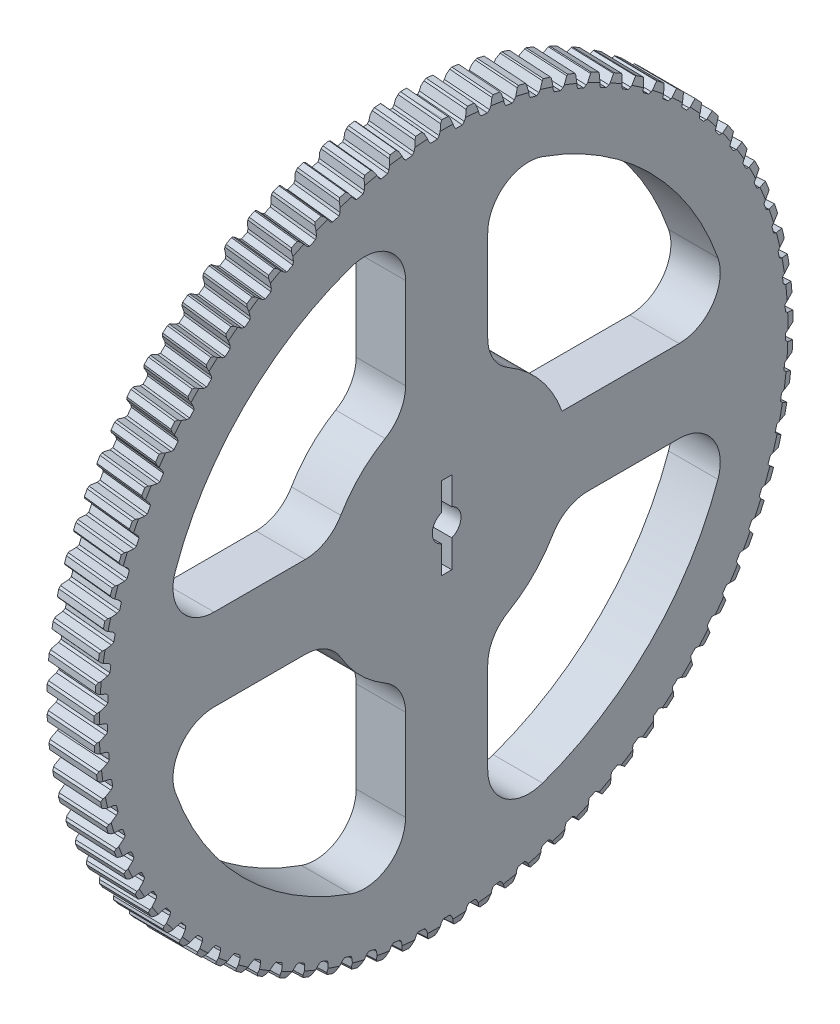
SolidWorks part; units mm, degrees
ref_plane "Front Plane" through (0, 0, 0) normal (0, 0, 1) x (1, 0, 0)
ref_plane "Top Plane" through (0, 0, 0) normal (0, 1, 0) x (1, 0, 0)
ref_plane "Right Plane" through (0, 0, 0) normal (1, 0, 0) x (0, 0, -1)
sketch "Sketch1" plane through (0, 0, 0) normal (1, 0, 0) x (0, 0, -1)
  line L0 (-56.5685, -10) -> (-34.4007, -10)
  line L1 (10, -34.4007) -> (10, -56.5685)
  line L3 (-10, 56.5685) -> (-10, 34.4007)
  line L5 (10, 56.5685) -> (10, 34.4007)
  line L7 (34.4007, -10) -> (56.5685, -10)
  line L11 (-56.5685, 10) -> (-34.4007, 10)
  line L17 (28.0636, 10) -> (56.5685, 10)
  line L24 (-10, -34.4007) -> (-10, -56.5685)
  circle A0 centre (0, 0) radius 82.5
  arc A1 (-23.3333, 65.9966) -> (-65.9966, 23.3333) centre (0, 0) ccw
  circle A2 centre (0, 0) radius 3.5
  arc A3 (-14.9739, 25.7556) -> (-25.7556, 14.9739) centre (0, 0) ccw
  arc A4 (-25.7556, -14.9739) -> (-14.9739, -25.7556) centre (0, 0) ccw
  arc A5 (-65.9966, -23.3333) -> (-23.3333, -65.9966) centre (0, 0) ccw
  arc A6 (28.0636, 10) -> (14.9739, 25.7556) centre (0, 0) ccw
  arc A7 (65.9966, 23.3333) -> (23.3333, 65.9966) centre (0, 0) ccw
  arc A8 (23.3333, -65.9966) -> (65.9966, -23.3333) centre (0, 0) ccw
  arc A9 (14.9739, -25.7556) -> (25.7556, -14.9739) centre (0, 0) ccw
  arc A10 (25.7556, -14.9739) -> (34.4007, -10) centre (34.4007, -20) cw
  arc A11 (10, -34.4007) -> (14.9739, -25.7556) centre (20, -34.4007) cw
  arc A12 (23.3333, -65.9966) -> (10, -56.5685) centre (20, -56.5685) cw
  arc A13 (65.9966, -23.3333) -> (56.5685, -10) centre (56.5685, -20) ccw
  arc A14 (56.5685, 10) -> (65.9966, 23.3333) centre (56.5685, 20) ccw
  arc A15 (10, 56.5685) -> (23.3333, 65.9966) centre (20, 56.5685) cw
  arc A16 (10, 34.4007) -> (14.9739, 25.7556) centre (20, 34.4007) ccw
  arc A17 (-25.7556, -14.9739) -> (-34.4007, -10) centre (-34.4007, -20) ccw
  arc A18 (-10, -34.4007) -> (-14.9739, -25.7556) centre (-20, -34.4007) ccw
  arc A19 (-23.3333, -65.9966) -> (-10, -56.5685) centre (-20, -56.5685) ccw
  arc A20 (-65.9966, -23.3333) -> (-56.5685, -10) centre (-56.5685, -20) cw
  arc A21 (-56.5685, 10) -> (-65.9966, 23.3333) centre (-56.5685, 20) cw
  arc A22 (-10, 56.5685) -> (-23.3333, 65.9966) centre (-20, 56.5685) ccw
  arc A23 (-14.9739, 25.7556) -> (-10, 34.4007) centre (-20, 34.4007) ccw
  arc A24 (-34.4007, 10) -> (-25.7556, 14.9739) centre (-34.4007, 20) ccw
  point P7 (0, 41.25)
  point P13 (-41.25, 0)
  point P20 (41.25, 0)
  point P24 (10, -28.0636)
  point P25 (0, -41.25)
  point P35 (69.282, 10)
  dimension "D1" = 165
  dimension "D2" = 140
  dimension "D3" = 7
  dimension "D5" = 10
  dimension "D4" = 20
extrude "Boss-Extrude1" add sketch "Sketch1" along normal blind 12
sketch "Sketch2" plane through (12, 0, 0) normal (1, 0, 0) x (0, 0, -1)
  line L0 (0, 0) -> (0, 124.1671) construction
  line L1 (-1.1664, 84.992) -> (-1.8254, 83.0029)
  line L2 (2.25, 82.4693) -> (1.8254, 83.0029)
  line L3 (0, 0) -> (-2.25, 82.4693) construction
  line L4 (0, 0) -> (-0.75, 85.4967) construction
  line L5 (-1.1664, 84.992) -> (-0.75, 85.4967)
  line L6 (-2.25, 82.4693) -> (-1.8254, 83.0029)
  line L7 (1.1664, 84.992) -> (1.8254, 83.0029)
  line L8 (1.1664, 84.992) -> (0.75, 85.4967)
  line L9 (-2.25, 82.4693) -> (-2.2382, 82.0352)
  line L10 (2.25, 82.4693) -> (2.25, 82.0349)
  arc A1 (0.75, 85.4967) -> (-0.75, 85.4967) centre (0, 0) ccw
  arc A2 (2.25, 82.0349) -> (-2.2382, 82.0352) centre (0, 0) ccw
  dimension "D1" = 171
  dimension "D2" = 2.25
  dimension "D6" = 1.5
sketch3d "3DSketch2"
  line L0 (12, 85.5, 0) -> (-0.4524, 85.5, -1.0894)
  line L1 (12, 0, 0) -> (12, 124.1671, 0) construction
  line L2 (12, 85.5, 0) -> (12, 85.5, -8.9262) construction
  arc A0 (12, 85.4967, -0.75) -> (12, 85.4967, 0.75) centre (12, 0, 0) ccw construction
  point P5 (97.5, 0, 0)
  dimension "D1" = 85
  dimension "D2" = 12.5
sweep "Sweep1" add profiles "Sketch2" path "3DSketch2"
pattern_circular "CirPattern1" count 85 over 360 about axis through (12, 0, 0) along (1, 0, 0) of "Sweep1"
sketch "Sketch4" plane through (12, 0, 0) normal (1, 0, 0) x (0, 0, -1)
  line L0 (0, 0) -> (0, 18.7674) construction
  line L3 (-1.25, -10) -> (1.25, -10)
  line L4 (-1.25, -10) -> (-1.25, 10)
  line L5 (-1.25, 10) -> (1.25, 10)
  line L6 (1.25, -10) -> (1.25, 10)
  line L7 (-1.25, -10) -> (1.25, 10) construction
  line L8 (-1.25, 10) -> (1.25, -10) construction
  point P9 (0, 0)
  dimension "D1" = 2.5
  dimension "D2" = 20
extrude "Cut-Extrude1" cut sketch "Sketch4" against normal blind 12
sketch "Sketch5" plane through (0, 0, 0) normal (0, 1, 0) x (1, 0, 0)
  line L0 (-0.4524, -0.7359) -> (46.524, -0.7359) construction
  line L1 (46.524, -0.7359) -> (6, -0.0811) construction
  line L3 (6, -0.0811) -> (6, 128.7084) construction
  line L4 (0, 83.2641) -> (0, 58.642)
  line L5 (12, 58.642) -> (12, 83.0413)
  line L6 (12, 83.0413) -> (11.5, 84.7641)
  line L7 (11.5, 84.7641) -> (0.5, 84.7641)
  line L8 (0.5, 84.7641) -> (0, 83.2641)
  line L9 (0, 58.642) -> (-27.8985, 58.642)
  line L10 (-27.8985, 58.642) -> (-27.8985, 128.7084)
  line L11 (-27.8985, 128.7084) -> (39.1543, 128.7084)
  line L12 (39.1543, 128.7084) -> (39.1543, 58.642)
  line L13 (39.1543, 58.642) -> (12, 58.642)
  line L17 (12, 1.8254) -> (12, 1.1664) construction
  point P5 (5.845, -0.0811)
  point P8 (12, 80.0247)
  point P15 (-0.3101, 81.3762)
  point P19 (11.845, 84.3452)
  point P21 (0, 0)
  point P22 (-0.155, 96.7712)
  point P23 (10.7793, 96.8317)
  point P24 (0, 0)
  point P25 (0.345, 81.3673)
  point P26 (0, 0)
  point P28 (12, 83.0413)
  dimension "D1" = 6
  dimension "D2" = 11
  dimension "D3" = 84
  dimension "D4" = 171
  dimension "D5" = 6
revolve "Cut-Revolve1" cut sketch "Sketch5" angle 360 about L0
